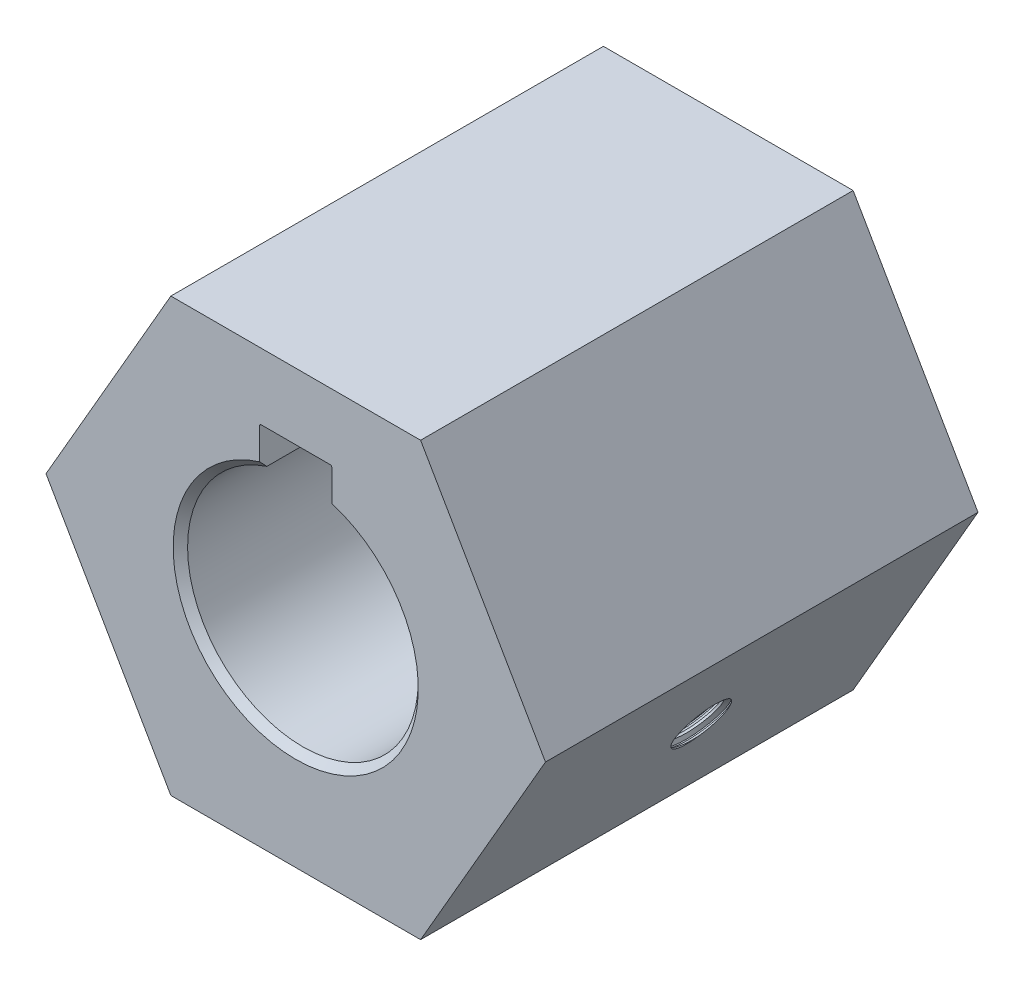
SolidWorks part; units mm, degrees
material "6061-T6 (SS)"
ref_plane "Front Plane" through (0, 0, 0) normal (0, 0, 1) x (1, 0, 0)
ref_plane "Top Plane" through (0, 0, 0) normal (0, 1, 0) x (1, 0, 0)
ref_plane "Right Plane" through (0, 0, 0) normal (1, 0, 0) x (0, 0, -1)
ref_plane "Plane1" through (0, 0, -15) normal (0, 0, -1) x (-1, 0, 0)
sketch "Sketch1" plane through (0, 0, -15) normal (0, 0, -1) x (-1, 0, 0)
  line L0 (-8.6603, 15) -> (-17.3205, 0)
  line L1 (-17.3205, 0) -> (-8.6603, -15)
  line L2 (-8.6603, -15) -> (8.6603, -15)
  line L3 (8.6603, -15) -> (17.3205, 0)
  line L4 (17.3205, 0) -> (8.6603, 15)
  line L5 (8.6603, 15) -> (-8.6603, 15)
extrude "Boss-Extrude1" add sketch "Sketch1" against normal blind 30
sketch "Sketch2" plane through (0, 0, 15) normal (0, 0, 1) x (1, 0, 0)
  line L0 (-2.5, 10.4) -> (-2.5, 7.5993)
  line L1 (2.5, 7.5993) -> (2.5, 10.4)
  line L2 (2.5, 10.4) -> (-2.5, 10.4)
  arc A0 (-2.5, 7.5993) -> (2.5, 7.5993) centre (0, 0) cw
extrude "Cut-Extrude1" cut sketch "Sketch2" against normal through all
ref_plane "Plane2" through (0, 0, 0) normal (0, -1, 0) x (1, 0, 0)
sketch "Sketch3" plane through (0, 0, 0) normal (0, -1, 0) x (1, 0, 0)
  line L0 (8, 15) -> (0, 15)
  line L1 (0, 15) -> (0, -15)
  line L2 (0, -15) -> (8, -15)
  line L3 (8, -15) -> (8, 15)
  line L4 (0, 15) -> (0, -15) construction
revolve "Cut-Revolve1" cut sketch "Sketch3" angle 360 about L4 reverse direction yes
hole_wizard "Ø4.2 (4.2) Diameter Hole1" positions "Sketch5" profile "Sketch4" hole size "Ø4.2" standard "ANSI Metric"
sketch "Sketch5" plane through (0, -15, 0) normal (0, -1, 0) x (-1, 0, 0)
  point P0 (0, 5)
sketch "Sketch4" plane through (0, -15, -5) normal (1, 0, 0) x (0, 0, -1)
  line L0 (0, 0) -> (0, 7)
  line L1 (0, 7) -> (2.1, 7)
  line L2 (2.1, 7) -> (2.1, 0)
  line L5 (2.1, 0) -> (0, 0)
  line L11 (0, -6.35) -> (0, 107.95) construction
  dimension "Thru Hole Dia." = 4.2
  dimension "Thru Hole Depth" = 7
chamfer "Chamfer1" distance 0.5 angle 45 2 edges at (0, -8, 15) (0, -8, -15)
fillet "Fillet1" radius 0.1 2 edges at (-2.5, 10.4, 0) (2.5, 10.4, 0) tangent propagation no
chamfer "Chamfer2" distance 1.15 angle 45 1 edges at (0, -15, -7.1)
sketch "Sketch6" plane through (-12.9904, 7.5, 0) normal (-0.866, 0.5, 0) x (0, 0, 1)
  circle A0 centre (0, 0) radius 1.75
  dimension "D1" = 3.5
extrude "Cut-Extrude2" cut sketch "Sketch6" against normal blind 4.8777 contours A0
thread "Thread1" pitch 0.6 method cut trim with start face yes trim with end face yes profile "Thread Profile1" start angle 0, offset 1, length 0, pitch 0.6, diameter 3.5
ref_plane "Plane3" through (-13.8564, 8, -1.75) normal (-0.5, -0.866, 0) x (0, 0, -1)
sketch "Thread Profile1" plane through (-13.8564, 8, -1.75) normal (-0.5, -0.866, 0) x (0, 0, -1)
  line L0 (0, 0) -> (0, 0.6) construction
  line L1 (0, 0) -> (0.3248, 0.1875)
  line L2 (0.3248, 0.1875) -> (0.3248, 0.2625)
  line L3 (0.3248, 0.2625) -> (0, 0.45)
  line L4 (0.3248, 0.225) -> (0, 0.225) construction
  line L11 (0, 0) -> (0, 0.45)
  point P2 (0, 0)
  dimension "Pitch" = 0.6
  dimension "Profile_Angle" = 60
  dimension "Profile_Land" = 0.075
  dimension "Profile_Height" = 0.3248
sketch "Sketch9" plane through (12.9904, -7.5, 0) normal (0.866, -0.5, 0) x (0, 0, -1)
  circle A0 centre (0, 0) radius 1.75
  dimension "D1" = 3.5
extrude "Cut-Extrude3" cut sketch "Sketch9" against normal blind 4.8777
thread "Thread2" pitch 0.6 method cut trim with start face yes trim with end face yes profile "Thread Profile2" start angle 0, offset 1, length 0, pitch 0.6, diameter 3.5
ref_plane "Plane4" through (13.8564, -8, 1.75) normal (-0.5, -0.866, 0) x (0, 0, 1)
sketch "Thread Profile2" plane through (13.8564, -8, 1.75) normal (-0.5, -0.866, 0) x (0, 0, 1)
  line L0 (0, 0) -> (0, 0.6) construction
  line L1 (0, 0) -> (0.3248, 0.1875)
  line L2 (0.3248, 0.1875) -> (0.3248, 0.2625)
  line L3 (0.3248, 0.2625) -> (0, 0.45)
  line L4 (0.3248, 0.225) -> (0, 0.225) construction
  line L11 (0, 0) -> (0, 0.45)
  point P2 (0, 0)
  dimension "Pitch" = 0.6
  dimension "Profile_Angle" = 60
  dimension "Profile_Land" = 0.075
  dimension "Profile_Height" = 0.3248
